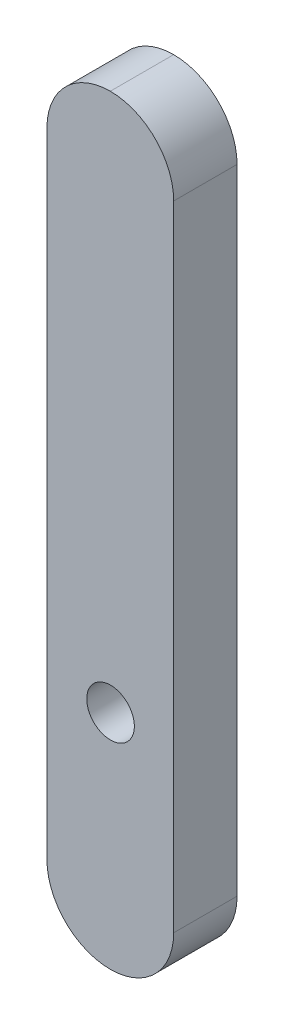
SolidWorks part; units mm, degrees
ref_plane "Front Plane" through (0, 0, 0) normal (0, 0, 1) x (1, 0, 0)
ref_plane "Top Plane" through (0, 0, 0) normal (0, 1, 0) x (1, 0, 0)
ref_plane "Right Plane" through (0, 0, 0) normal (1, 0, 0) x (0, 0, -1)
sketch "Sketch1" plane through (0, 0, 0) normal (0, 0, 1) x (1, 0, 0)
  line L1 (-6.3728, -22.2935) -> (6.3272, -22.2935)
  line L2 (-6.3728, -22.2935) -> (-6.3728, 53.9065)
  line L3 (-6.3728, 53.9065) -> (6.3272, 53.9065)
  line L4 (6.3272, -22.2935) -> (6.3272, 53.9065)
  dimension "D1" = 12.7
  dimension "D2" = 76.2
extrude "Boss-Extrude1" add sketch "Sketch1" along normal blind 6.35
sketch "Sketch2" plane through (0, 0, 0) normal (0, 0, -1) x (-1, 0, 0)
  circle A0 centre (0, 0) radius 2.3839
extrude "Cut-Extrude1" cut sketch "Sketch2" against normal through all
fillet "Fillet1" radius 6.35 4 edges at (6.3272, -22.2935, 3.175) (-6.3728, -22.2935, 3.175) (6.3272, 53.9065, 3.175) (-6.3728, 53.9065, 3.175)
